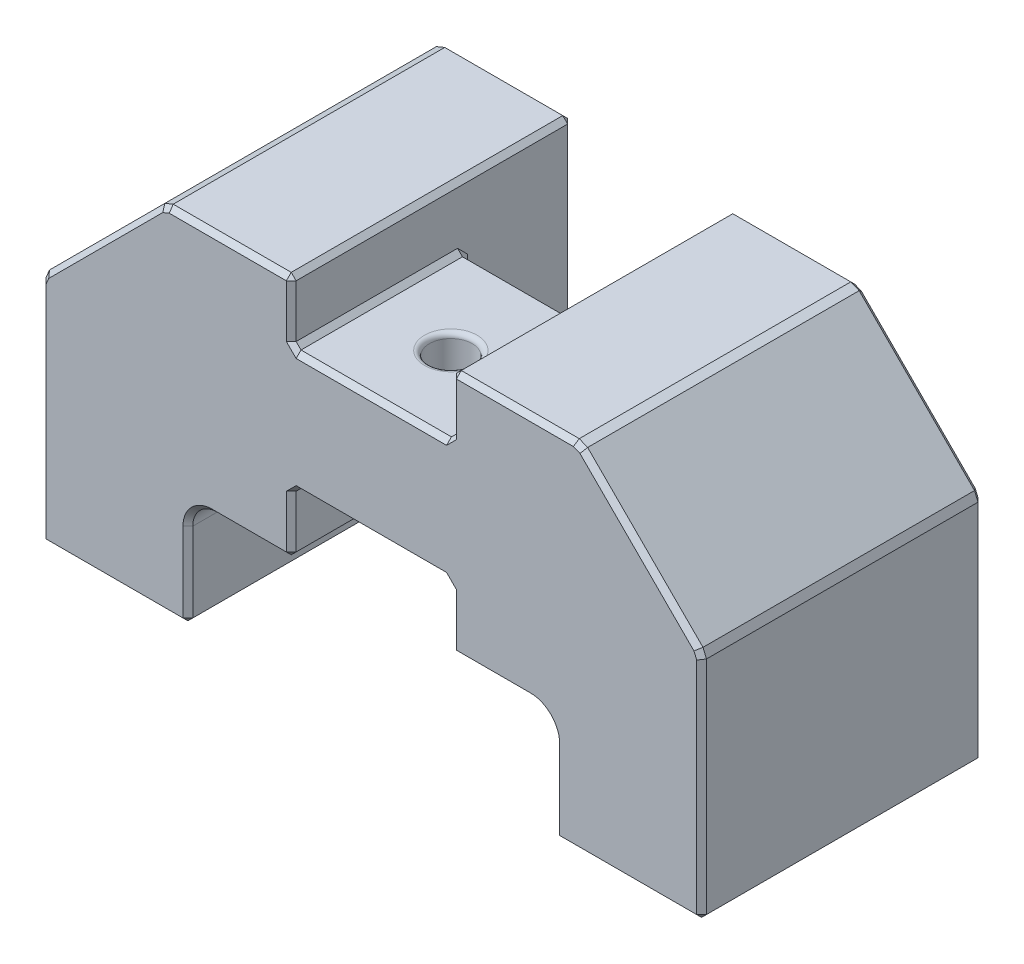
SolidWorks part; units mm, degrees
note: The reader was unsure of these and kept them because the rebuilt part matched: shared geometry of "Sketch1<4>".
ref_plane "Front Plane" through (0, 0, 0) normal (0, 0, 1) x (1, 0, 0)
ref_plane "Top Plane" through (0, 0, 0) normal (0, 1, 0) x (1, 0, 0)
ref_plane "Right Plane" through (0, 0, 0) normal (1, 0, 0) x (0, 0, -1)
sketch "Sketch1" plane through (0, 0, 0) normal (0, 0, 1) x (1, 0, 0)
  line L0 (0, 45.3438) -> (0, 0) construction
  line L1 (0, 0) -> (45.3438, 0) construction
  line L2 (-15, 6.1) -> (15, 6.1) construction
  line L3 (-12.5, 15) -> (12.5, 15) construction
  line L4 (-15, 12.5) -> (-15, -12.5) construction
  line L5 (-12.5, -15) -> (12.5, -15) construction
  line L6 (15, 12.5) -> (15, -12.5) construction
  line L7 (-15, -6.1) -> (15, -6.1) construction
  line L8 (-15, -12.5) -> (-15, 13)
  line L9 (-13, 15) -> (13, 15)
  line L10 (15, 13) -> (15, -12.5)
  line L11 (15, -12.5) -> (27, -12.5)
  line L12 (27, -12.5) -> (27, 35)
  line L13 (27, 35) -> (-27, 35)
  line L14 (-27, 35) -> (-27, -12.5)
  line L15 (-27, -12.5) -> (-15, -12.5)
  line L16 (6.55, 29.9) -> (6.55, 20.1)
  line L17 (-6.55, 20.1) -> (6.55, 20.1)
  line L18 (-6.55, 20.1) -> (-6.55, 15)
  line L19 (-6.55, 15) -> (6.55, 15)
  line L20 (6.55, 20.1) -> (6.55, 15)
  line L21 (-6.55, 35) -> (6.55, 35)
  line L22 (-6.55, 35) -> (-6.55, 29.9)
  line L23 (-6.55, 29.9) -> (6.55, 29.9)
  line L24 (6.55, 35) -> (6.55, 29.9)
  line L25 (-6.55, 29.9) -> (-6.55, 20.1)
  line L26 (-15, 6.1) -> (-27, 6.1)
  line L27 (15, 6.1) -> (27, 6.1)
  arc A0 (-15, -12.5) -> (-12.5, -15) centre (-12.5, -12.5) ccw construction
  arc A1 (12.5, -15) -> (15, -12.5) centre (12.5, -12.5) ccw construction
  arc A2 (15, 12.5) -> (12.5, 15) centre (12.5, 12.5) ccw construction
  arc A3 (-12.5, 15) -> (-15, 12.5) centre (-12.5, 12.5) ccw construction
  arc A4 (15, 13) -> (13, 15) centre (13, 13) ccw
  arc A5 (-13, 15) -> (-15, 13) centre (-13, 13) ccw
  point P10 (-15, -15)
  point P13 (15, -15)
  point P18 (-15, 15)
  point P33 (-15, 15)
  dimension "D3" = 2.5
  dimension "D5" = 2
  dimension "D1" = 30
  dimension "D2" = 30
  dimension "D4" = 12.2
  dimension "D6" = 12
  dimension "D7" = 20
  dimension "D8" = 5.1
  dimension "D9" = 5.1
  dimension "D10" = 13.1
extrude "Boss-Extrude1" add sketch "Sketch1" along normal blind 23 contours A4 L10 L11 L12 L13 L24 L16 L20 L9 | A5 L9 L18 L25 L22 L13 L14 L15 L8 | L23 L25 L17 L16
extrude "Cut-Extrude1" cut sketch "Sketch1<4>" along normal blind 9 contours L23 L25 L17 L16
sketch "Sketch1<4>" plane through (0, 0, 0) normal (0, 0, 1) x (1, 0, 0) same geometry as "Sketch1"
chamfer "Chamfer4" distance 10 angle 45 2 edges at (27, 35, 11.5) (-27, 35, 11.5)
chamfer "Chamfer6" distance 0.4 4 edges at (-27, 25, 11.5) (-17, 35, 11.5) (17, 35, 11.5) (27, 25, 11.5)
sketch "Sketch6" plane through (0, 29.9, 0) normal (0, 1, 0) x (1, 0, 0)
  line L0 (0, 0) -> (0, -35.5) construction
  circle A0 centre (0, -16.5) radius 1.75
  circle A1 centre (0, -29.5) radius 5
  circle A2 centre (0, -29.5) radius 2.55
  point P10 (0, 0)
  dimension "D1" = 16.5
  dimension "D2" = 3.5
  dimension "D4" = 10
  dimension "D5" = 5.1
  dimension "D3" = 6
extrude "Cut-Extrude5" cut sketch "Sketch6" against normal through all contours A0 L0 | L0 A0
fillet "Fillet1" radius 0.4 1 edges at (0, 29.9, 18.25)
chamfer "Chamfer7" distance 0.4 angle 45 60 edges at (15, 9.55, 23) (16.9414, 34.8586, 0) (21, 6.1, 23) (27, 15.35, 23) (9.775, 15, 0) (6.55, 25, 0) (-6.55, 25, 0) (-9.775, 15, 0) (-14.4142, 14.4142, 0) (-15, 9.55, 0) (-21, 6.1, 0) (-11.575, 35, 0) (27, 15.35, 0) (21, 6.1, 0) (15, 9.55, 0) (14.4142, 14.4142, 0) (6.55, 32.45, 23) (6.55, 15, 11.5) (6.55, 20.1, 16) (-6.55, 20.1, 16) (-6.55, 15, 11.5) (-15, 6.1, 11.5) (-27, 6.1, 11.5) (-6.55, 35, 11.5) (-6.55, 29.9, 16) (6.55, 29.9, 16) (6.55, 35, 11.5) (27, 6.1, 11.5) (15, 6.1, 11.5) (0, 29.9, 23) (-6.55, 32.45, 23) (-11.575, 35, 23) (14.4142, 14.4142, 23) (-21, 6.1, 23) (0, 29.9, 9) (6.55, 25, 9) (-6.55, 25, 9) (0, 20.1, 9) (-15, 9.55, 23) (-14.4142, 14.4142, 23) (-9.775, 15, 23) (-6.55, 17.55, 23) (0, 20.1, 23) (-27, 15.35, 23) (-27, 15.35, 0) (6.55, 17.55, 23) (-22, 30, 0) (-16.9414, 34.8586, 0) (-26.8586, 24.9414, 0) (-22, 30, 23) (22, 30, 23) (9.775, 15, 23) (11.575, 35, 23) (26.8586, 24.9414, 23) (16.9414, 34.8586, 23) (-16.9414, 34.8586, 23) (-26.8586, 24.9414, 23) (11.575, 35, 0) (22, 30, 0) (26.8586, 24.9414, 0)
